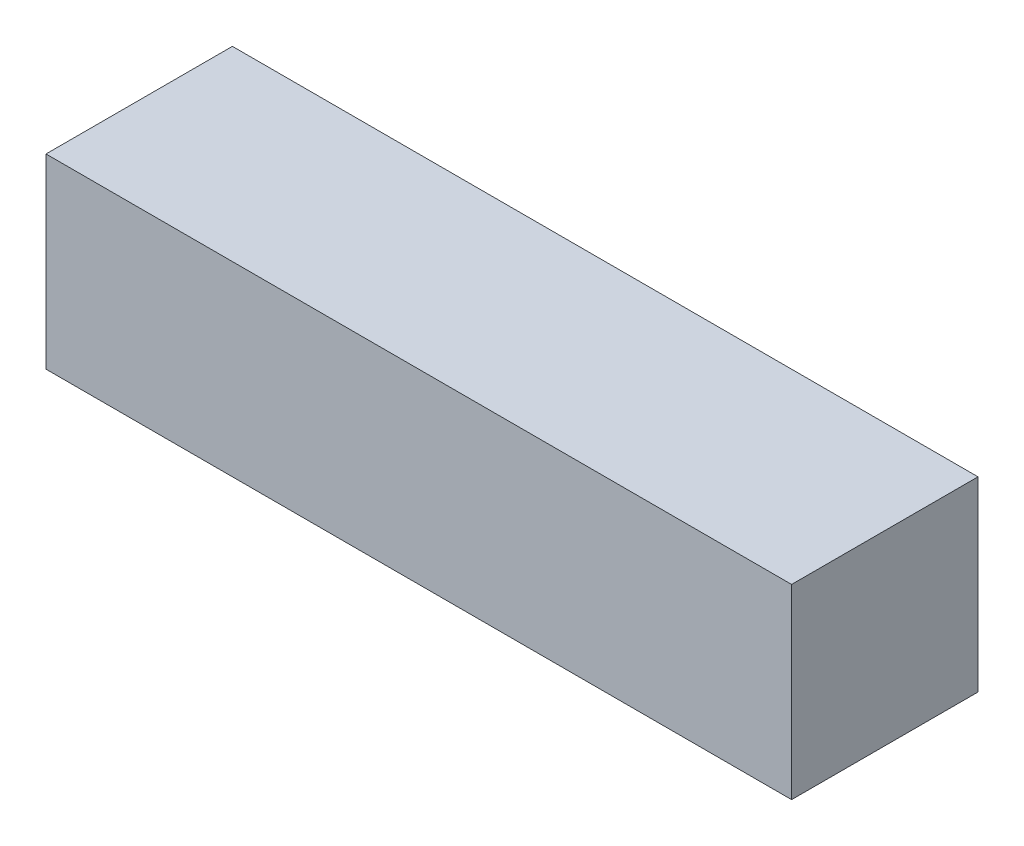
SolidWorks part; units mm, degrees
material "Custom Plastic"
ref_plane "X-Y Datum" through (0, 0, 0) normal (0, 0, 1) x (1, 0, 0)
ref_plane "X-Z Datum" through (0, 0, 0) normal (0, 1, 0) x (1, 0, 0)
ref_plane "Y-Z Datum" through (0, 0, 0) normal (1, 0, 0) x (0, 0, -1)
sketch "Sketch1" plane through (0, 0, 0) normal (0, 0, 1) x (1, 0, 0)
  line L1 (-19.05, 4.7625) -> (19.05, 4.7625)
  line L2 (-19.05, 4.7625) -> (-19.05, -4.7625)
  line L3 (-19.05, -4.7625) -> (19.05, -4.7625)
  line L4 (19.05, 4.7625) -> (19.05, -4.7625)
  line L5 (-19.05, 4.7625) -> (19.05, -4.7625) construction
  line L6 (-19.05, -4.7625) -> (19.05, 4.7625) construction
  point P0 (0, 0)
  dimension "D1" = 38.1
  dimension "D2" = 9.525
extrude "Boss-Extrude1" add sketch "Sketch1" along normal blind 9.525
